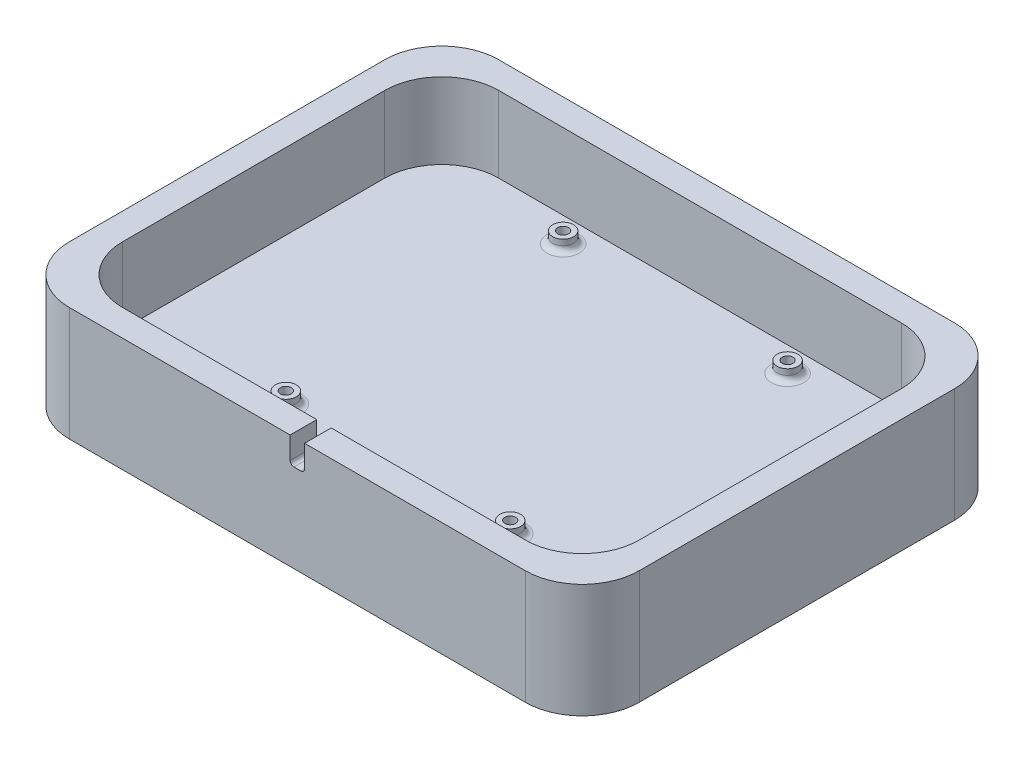
SolidWorks part; units mm, degrees
ref_plane "Front Plane" through (0, 0, 0) normal (0, 0, 1) x (1, 0, 0)
ref_plane "Top Plane" through (0, 0, 0) normal (0, 1, 0) x (1, 0, 0)
ref_plane "Right Plane" through (0, 0, 0) normal (1, 0, 0) x (0, 0, -1)
sketch "Sketch1" plane through (0, 0, 0) normal (0, 1, 0) x (1, 0, 0)
  line L1 (-75, 50) -> (75, 50)
  line L2 (-75, 50) -> (-75, -50)
  line L3 (-75, -50) -> (75, -50)
  line L4 (75, 50) -> (75, -50)
  line L5 (-75, 50) -> (75, -50) construction
  line L6 (-75, -50) -> (75, 50) construction
  point P0 (0, 0)
  dimension "D1" = 150
  dimension "D2" = 100
extrude "Boss-Extrude1" add sketch "Sketch1" along normal blind 10
sketch "Sketch2" plane through (0, 10, 0) normal (0, 1, 0) x (1, 0, 0)
  line L0 (75, -50) -> (75, 50) construction
  line L1 (0, 0) -> (0, 70.2566) construction
  line L2 (75, 50) -> (-75, 50) construction
  line L3 (0, 0) -> (146.4068, 0) construction
  circle A1 centre (29.54, 36.5) radius 2.75
  circle A2 centre (29.54, -36.5) radius 2.75
  circle A3 centre (-29.54, -36.5) radius 2.75
  circle A4 centre (-29.54, 36.5) radius 2.75
  point P0 (29.54, 36.5)
  point P8 (-29.54, -36.5)
  point P9 (29.54, -36.5)
  point P16 (-29.54, 36.5)
  dimension "D5" = 5.5
  dimension "D1" = 45.46
  dimension "D2" = 13.5
extrude "Boss-Extrude2" add sketch "Sketch2" along normal blind 3
hole_wizard "Ø1.0mm Dowel Hole1" positions "Sketch3" profile "Sketch4" hole size "Ø1.0" standard "ISO"
sketch "Sketch3" plane through (0, 13, 0) normal (0, 1, 0) x (1, 0, 0)
  point P0 (-29.54, 36.5)
  point P3 (29.54, 36.5)
  point P6 (29.54, -36.5)
  point P9 (-29.54, -36.5)
sketch "Sketch4" plane through (-29.54, 13, -36.5) normal (1, 0, 0) x (0, 0, 1)
  line L0 (0, 0) -> (0, 10.8562)
  line L1 (0, 10.8562) -> (1.425, 10)
  line L2 (1.425, 10) -> (1.425, 0)
  line L5 (1.425, 0) -> (0, 0)
  line L10 (0, 10.8562) -> (-1.425, 10) construction
  line L11 (0, -6.35) -> (0, 107.95) construction
  dimension "Hole Dia." = 2.85
  dimension "Hole Depth" = 10
  dimension "Drill Angle" = 118
fillet "Fillet1" radius 1.5 4 edges at (29.54, 10, 33.75) (-29.54, 10, 39.25) (29.54, 10, -33.75) (-29.54, 10, -39.25)
sketch "Sketch5" plane through (0, 0, 0) normal (0, -1, 0) x (1, 0, 0)
  line L1 (-75, 50) -> (75, 50)
  line L2 (-75, 50) -> (-75, 63)
  line L3 (-75, 63) -> (75, 63)
  line L4 (75, 50) -> (75, 63)
  dimension "D1" = 13
extrude "Boss-Extrude3" add sketch "Sketch5" against normal blind 10
sketch "Sketch7" plane through (0, 10, 0) normal (0, 1, 0) x (1, 0, 0)
  line L1 (-75, 50) -> (75, 50)
  line L2 (-75, 50) -> (-75, -63)
  line L3 (-75, -63) -> (75, -63)
  line L4 (75, 50) -> (75, -63)
extrude "Extrude-Thin1" add sketch "Sketch7" along normal blind 20 thin thin type one direction reverse wall 7
sketch "Sketch8" plane through (0, 0, 63) normal (0, 0, 1) x (1, 0, 0)
  line L0 (0, 30) -> (0, 23.2) construction
  line L1 (-75, 30) -> (75, 30) construction
  line L2 (-1.9, 30) -> (1.9, 30)
  line L3 (1.9, 30) -> (1.9, 24.2)
  line L4 (0.9, 23.2) -> (-0.9, 23.2)
  line L5 (-1.9, 30) -> (-1.9, 24.2)
  arc A0 (1.9, 24.2) -> (0.9, 23.2) centre (0.9, 24.2) cw
  arc A1 (-1.9, 24.2) -> (-0.9, 23.2) centre (-0.9, 24.2) ccw
  dimension "D2" = 1
  dimension "D1" = 1.9
  dimension "D3" = 5.8
extrude "Cut-Extrude1" cut sketch "Sketch8" against normal up to next
fillet "Fillet2" radius 15 4 edges at (75, 15, 63) (75, 15, -50) (-75, 15, -50) (-75, 15, 63)
fillet "Fillet3" radius 15 4 edges at (-68, 20, -43) (-68, 20, 56) (68, 20, -43) (68, 20, 56)
